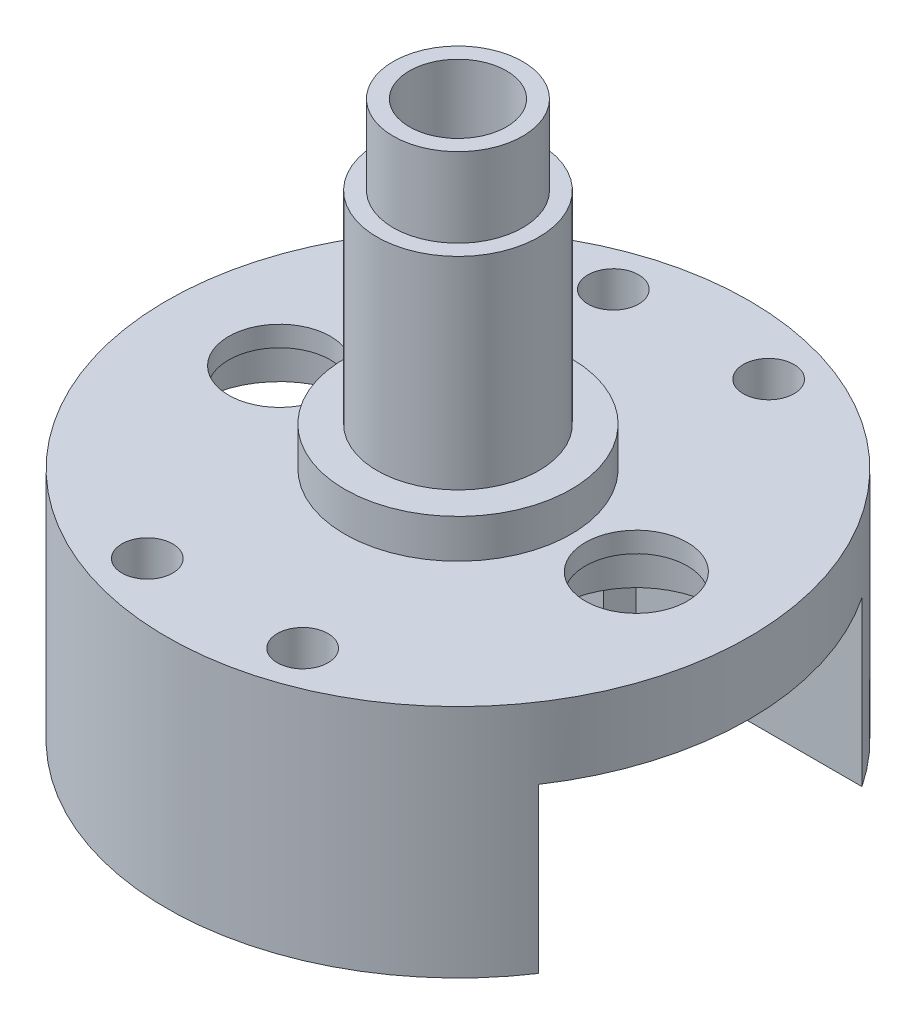
SolidWorks part; units mm, degrees
ref_plane "Front Plane" through (0, 0, 0) normal (0, 0, 1) x (1, 0, 0)
ref_plane "Top Plane" through (0, 0, 0) normal (0, 1, 0) x (1, 0, 0)
ref_plane "Right Plane" through (0, 0, 0) normal (1, 0, 0) x (0, 0, -1)
sketch "Sketch1" plane through (0, 0, 0) normal (0, 1, 0) x (1, 0, 0)
  circle A0 centre (0, 0) radius 11.1125
  circle A1 centre (0, 0) radius 4.7625
  dimension "D1" = 22.225
  dimension "D2" = 9.525
extrude "Boss-Extrude1" add sketch "Sketch1" along normal blind 3.81
sketch "Sketch2" plane through (0, 3.81, 0) normal (0, 1, 0) x (1, 0, 0)
  circle A0 centre (0, 0) radius 4.7625
  circle A1 centre (0, 0) radius 7.9375
  circle A2 centre (0, 0) radius 4.7625 construction
  dimension "D1" = 15.875
extrude "Boss-Extrude2" add sketch "Sketch2" along normal blind 19.8438
cosmetic thread "Cosmetic Thread2" parameters "D1"=11.2014, "D2"=14.1961
ref_plane "Plane1" through (0, 14.9225, 0) normal (0, 1, 0) x (-1, 0, 0)
sketch "Sketch5" plane through (0, 0, 0) normal (0, -1, 0) x (1, 0, 0)
  line L0 (-17.5, 0) -> (17.5, 0) construction
  circle A0 centre (0, 0) radius 7.9375
  circle A1 centre (0, 0) radius 17.5 construction
  circle A2 centre (17.5, 0) radius 5
  circle A3 centre (-17.5, 0) radius 5
  circle A4 centre (0, 0) radius 28.575
  dimension "D1" = 15.875
  dimension "D2" = 35
  dimension "D3" = 10
  dimension "D4" = 57.15
extrude "Boss-Extrude4" add sketch "Sketch5" along normal blind 7
sketch "Sketch6" plane through (0, -7, 0) normal (0, -1, 0) x (1, 0, 0)
  circle A0 centre (-17.5, 0) radius 8
  circle A1 centre (17.5, 0) radius 8
  dimension "D1" = 16
extrude "Cut-Extrude5" cut sketch "Sketch6" against normal blind 5
sketch "Sketch8" plane through (0, -7, 0) normal (0, -1, 0) x (1, 0, 0)
  line L0 (-23.7595, -15.875) -> (23.7595, -15.875)
  line L1 (-23.7595, 15.875) -> (23.7595, 15.875)
  line L2 (-23.7595, -15.875) -> (-23.7595, 15.875) construction
  line L3 (23.7595, -15.875) -> (23.7595, 15.875) construction
  circle A0 centre (0, 0) radius 28.575 construction
  circle M3 centre (0, 0) radius 28.575
  dimension "D1" = 31.75
extrude "Boss-Extrude5" add sketch "Sketch8" along normal blind 16.064 contours L0 M3 | L1 M3 region at (0, -7, -21.0662) region at (0, -7, 21.0662)
sketch "Sketch9" plane through (0, -23.064, 0) normal (0, -1, 0) x (1, 0, 0)
  line L0 (7.62, 22.86) -> (-7.62, 22.86) construction
  line L1 (17.5, 0) -> (0, 0) construction
  circle A0 centre (7.62, 22.86) radius 2.4892
  circle A1 centre (-7.62, 22.86) radius 2.4892
  circle A2 centre (-7.62, -22.86) radius 2.4892
  circle A3 centre (7.62, -22.86) radius 2.4892
  dimension "D3" = 4.9784
  dimension "D1" = 7.62
  dimension "D2" = 22.86
  dimension "D4" = 7.62
extrude "Cut-Extrude7" cut sketch "Sketch9" against normal up to surface (23.064 mm away) up to face at (-17.5, 0, -5)
sketch "Sketch11" plane through (0, 0, -15.875) normal (0, 0, 1) x (1, 0, 0)
  line L0 (1.5875, -23.064) -> (1.5875, -8.5875)
  line L1 (-23.7595, -23.064) -> (23.7595, -23.064) construction
  line L2 (-23.7595, -7) -> (23.7595, -7) construction
  line L3 (-1.5875, -23.064) -> (-1.5875, -8.5875)
  line L4 (1.5875, -23.064) -> (23.7595, -23.064) construction
  line L5 (-1.5875, -23.064) -> (-23.7595, -23.064) construction
  line L6 (23.7595, -23.064) -> (23.7595, -7) construction
  line L7 (-23.7595, -23.064) -> (-23.7595, -7) construction
  arc A0 (1.5875, -8.5875) -> (-1.5875, -8.5875) centre (0, -8.5875) ccw
  line M6 (-23.7595, -23.064) -> (23.7595, -23.064)
  dimension "D1" = 3.175
extrude "Cut-Extrude9" cut sketch "Sketch11" against normal through all contours L0 A0 L3 M6 region at (0, -15.1983, -15.875)
sketch "Sketch12" plane through (0, 23.6538, 0) normal (0, 1, 0) x (1, 0, 0)
  circle A0 centre (0, 0) radius 4.7625
  circle A1 centre (0, 0) radius 6.35
  circle A2 centre (0, 0) radius 4.7625 construction
  dimension "D1" = 12.7
extrude "Boss-Extrude6" add sketch "Sketch12" along normal blind 7.7787
ref_plane "Plane2" through (0, -23.064, 0) normal (0, -1, 0) x (1, 0, 0)
ref_axis "Axis1" through (0, 31.4325, 0) along (0, -1, 0)
ref_axis "Axis2" through (-17.5, -2, 0) along (0, -1, 0)
ref_axis "Axis3" through (17.5, -2, 0) along (0, -1, 0)
ref_plane "Plane3" through (0, -2, 0) normal (0, -1, 0) x (-1, 0, 0)
